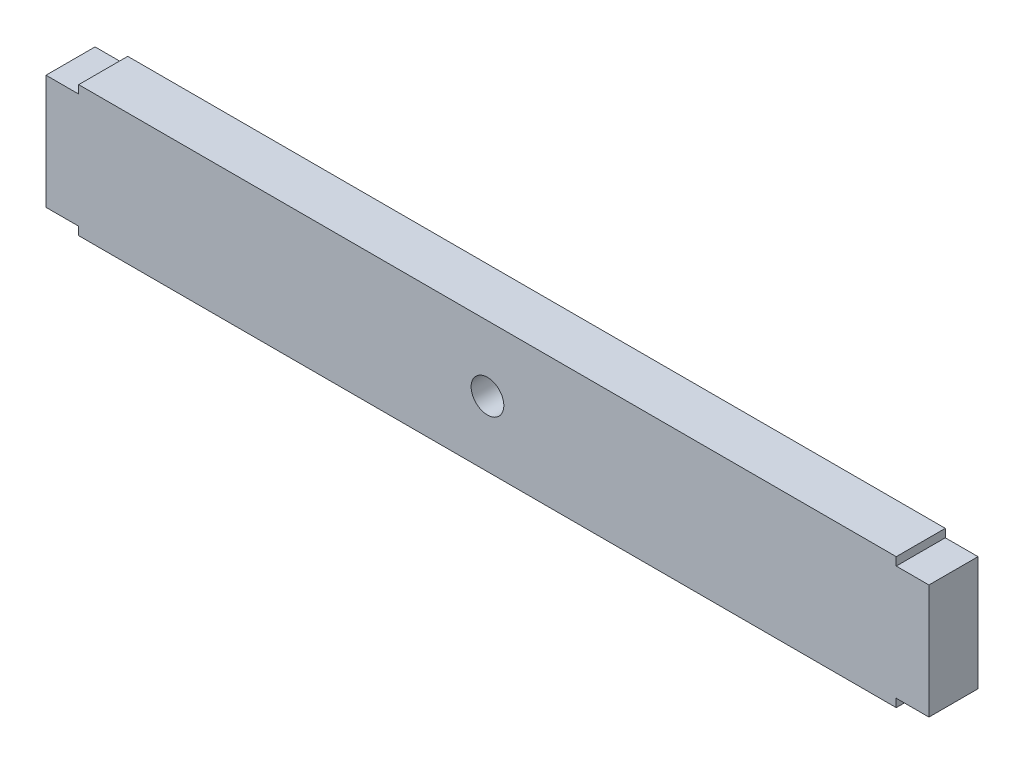
SolidWorks part; units mm, degrees
material "铜"
ref_plane "前视基准面" through (0, 0, 0) normal (0, 0, 1) x (1, 0, 0)
ref_plane "上视基准面" through (0, 0, 0) normal (0, 1, 0) x (1, 0, 0)
ref_plane "右视基准面" through (0, 0, 0) normal (1, 0, 0) x (0, 0, -1)
sketch "草图1" plane through (0, 0, 0) normal (0, 0, 1) x (1, 0, 0)
  line L1 (250, -40) -> (-250, -40)
  line L2 (250, -40) -> (250, 40)
  line L3 (250, 40) -> (-250, 40)
  line L4 (-250, -40) -> (-250, 40)
  line L5 (250, -40) -> (-250, 40) construction
  line L6 (250, 40) -> (-250, -40) construction
  line L7 (-250, -35) -> (-270, -35)
  line L8 (-250, -35) -> (-250, 35)
  line L9 (-250, 35) -> (-270, 35)
  line L10 (-270, -35) -> (-270, 35)
  line L11 (250, -35) -> (270, -35)
  line L12 (250, -35) -> (250, 35)
  line L13 (250, 35) -> (270, 35)
  line L14 (270, -35) -> (270, 35)
  circle A0 centre (0, 0) radius 10
  point P0 (0, 0)
  dimension "D9" = 20
  dimension "D1" = 500
  dimension "D2" = 80
  dimension "D3" = 70
  dimension "D4" = 20
  dimension "D5" = 5
  dimension "D6" = 70
  dimension "D7" = 5
  dimension "D8" = 20
extrude "凸台-拉伸1" add sketch "草图1" along normal blind 30 contours L4 L1 L2 L3 | L10 L7 L4 L9 | L14 L13 L12 L11 region at (0, -34.9364, 0) region at (-260, 0, 0)
